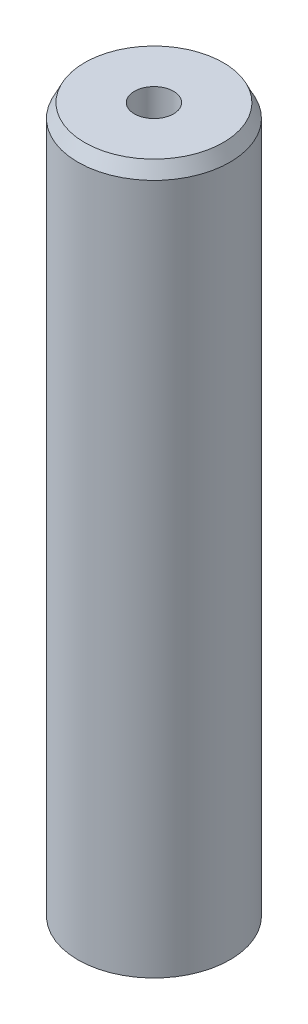
SolidWorks part; units mm, degrees
ref_plane "Front Plane" through (0, 0, 0) normal (0, 0, 1) x (1, 0, 0)
ref_plane "Top Plane" through (0, 0, 0) normal (0, 1, 0) x (1, 0, 0)
ref_plane "Right Plane" through (0, 0, 0) normal (1, 0, 0) x (0, 0, -1)
sketch "Sketch1" plane through (0, 0, 0) normal (0, 1, 0) x (1, 0, 0)
  circle A0 centre (0, 0) radius 10
  dimension "SHAFT_OD" = 20
extrude "Boss-Extrude1" add sketch "Sketch1" along normal blind 93.5189
sketch "Sketch2" plane through (0, 0, 0) normal (0, 1, 0) x (1, 0, 0)
  circle A0 centre (0, 0) radius 2.5775
  dimension "BORE_D" = 5.1549
extrude "Cut-Extrude1" cut sketch "Sketch2" along normal through all
chamfer "Chamfer1" distance 1.7952 angle 26.3 2 edges at (0, 93.5189, 10) (0, 0, 10) first distance on face at (0, 93.5189, 10) first distance on face at (0, 0, 2.5775)
